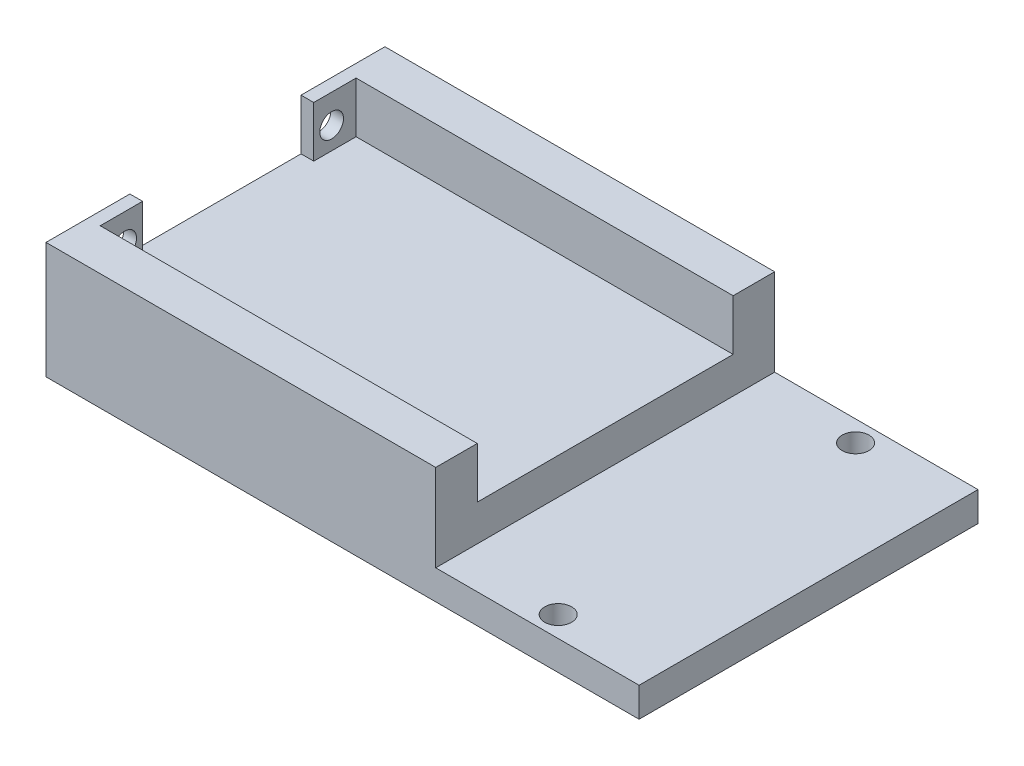
SolidWorks part; units mm, degrees
ref_plane "Front Plane" through (0, 0, 0) normal (0, 0, 1) x (1, 0, 0)
ref_plane "Top Plane" through (0, 0, 0) normal (0, 1, 0) x (1, 0, 0)
ref_plane "Right Plane" through (0, 0, 0) normal (1, 0, 0) x (0, 0, -1)
sketch "Sketch1" plane through (0, 0, 0) normal (0, 0, 1) x (1, 0, 0)
  line L0 (140, 0) -> (0, 0)
  line L1 (0, 0) -> (0, 15.49)
  line L2 (0, 15.49) -> (92, 15.49)
  line L3 (92, 15.49) -> (92, 6.96)
  line L4 (92, 6.96) -> (140, 6.96)
  line L5 (140, 6.96) -> (140, 0)
  dimension "D1" = 92
  dimension "D2" = 6.96
  dimension "D3" = 15.49
  dimension "D4" = 140
extrude "Boss-Extrude1" add sketch "Sketch1" along normal blind 80
sketch "Sketch2" plane through (0, 15.49, 0) normal (0, 1, 0) x (1, 0, 0)
  line L0 (0, 0) -> (0, -9.8)
  line L1 (0, -80) -> (0, 0) construction
  line L2 (3, -9.8) -> (92, -9.8)
  line L3 (92, -80) -> (92, 0) construction
  line L4 (92, -9.8) -> (92, 0)
  line L5 (92, 0) -> (0, 0)
  line L6 (0, -80) -> (92, -80)
  line L7 (92, -80) -> (92, -70.2)
  line L8 (92, -70.2) -> (3, -70.2)
  line L9 (0, -70.2) -> (0, -80)
  line L10 (0, -60.2) -> (3, -60.2)
  line L11 (3, -60.2) -> (3, -70.2)
  line L13 (0, -9.8) -> (0, -19.8)
  line L14 (0, -19.8) -> (3, -19.8)
  line L15 (3, -19.8) -> (3, -9.8)
  line M3 (92, 0) -> (0, 0)
  line M4 (0, 0) -> (0, -80)
  line M5 (0, -80) -> (92, -80)
  line M6 (92, -80) -> (92, 0)
  dimension "D1" = 9.8
  dimension "D2" = 9.8
  dimension "D3" = 10
  dimension "D4" = 3
  dimension "D5" = 10
  dimension "D6" = 3
  dimension "D7" = 9.8
  dimension "D8" = 9.8
extrude "Boss-Extrude2" add sketch "Sketch2" along normal blind 12 contours L14 L15 L2 M6 M3 M4 | L11 L10 L8 M4 M5 M6 region at (44.567, 15.49, 5.2188) region at (44.567, 15.49, 74.7812)
sketch "Sketch3" plane through (0, 0, 0) normal (-1, 0, 0) x (0, 0, 1)
  line L0 (19.8, 20.72) -> (15.57, 20.72) construction
  line L2 (15.57, 20.72) -> (15.57, 27.49) construction
  line L3 (0, 27.49) -> (19.8, 27.49) construction
  line L4 (60.2, 20.72) -> (64.43, 20.72) construction
  line L6 (64.43, 20.72) -> (64.43, 27.49) construction
  line L7 (60.2, 27.49) -> (80, 27.49) construction
  line L8 (19.8, 27.49) -> (19.8, 15.49) construction
  line L9 (60.2, 27.49) -> (60.2, 15.49) construction
  circle A0 centre (15.57, 20.72) radius 2.795
  circle A1 centre (64.43, 20.72) radius 2.795
extrude "Cut-Extrude1" cut sketch "Sketch3" against normal blind 60
sketch "Sketch4" plane through (0, 6.96, 0) normal (0, 1, 0) x (1, 0, 0)
  line L0 (92, -4.9) -> (140, -4.9) construction
  line L1 (92, -9.8) -> (92, 0) construction
  line L2 (140, -80) -> (140, 0) construction
  line L3 (92, -75.1) -> (140, -75.1) construction
  line L4 (92, -80) -> (92, -70.2) construction
  circle A0 centre (116, -4.9) radius 3.175
  circle A1 centre (116, -75.1) radius 3.175
  dimension "D1" = 6.35
  dimension "D2" = 6.35
extrude "Cut-Extrude2" cut sketch "Sketch4" against normal blind 10
